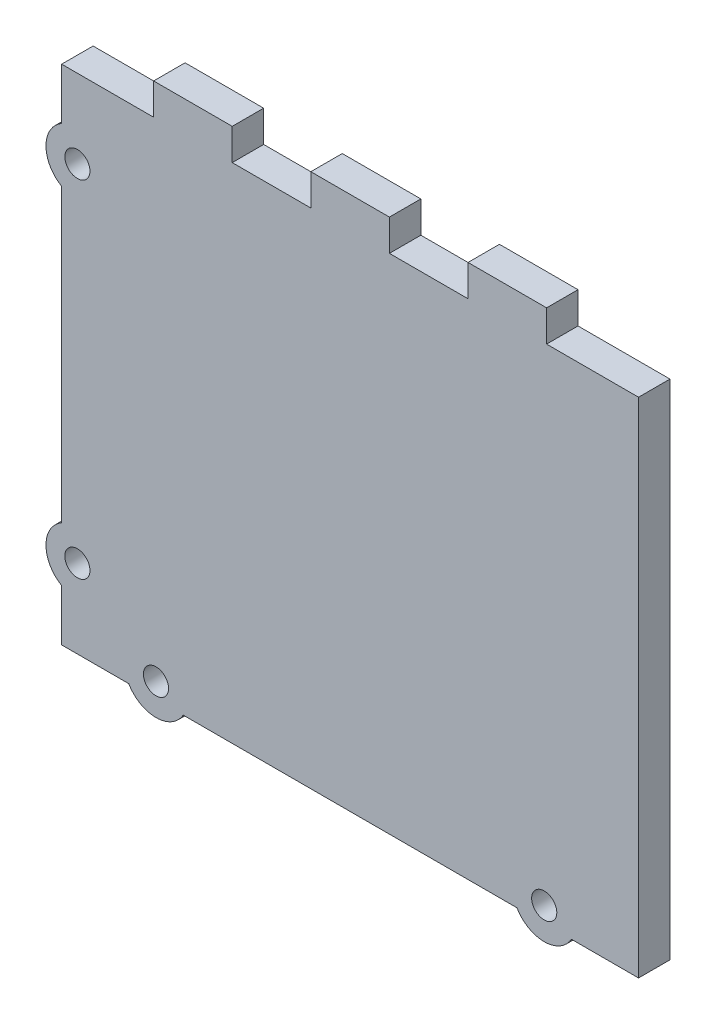
SolidWorks part; units mm, degrees
ref_plane "Front Plane" through (0, 0, 0) normal (0, 0, 1) x (1, 0, 0)
ref_plane "Top Plane" through (0, 0, 0) normal (0, 1, 0) x (1, 0, 0)
ref_plane "Right Plane" through (0, 0, 0) normal (1, 0, 0) x (0, 0, -1)
sketch "Sketch1" plane through (0, 0, 0) normal (0, 0, 1) x (1, 0, 0)
  line L0 (-23, -34.2) -> (-36.4, -34.2) construction
  line L2 (-36.5, 29.8) -> (-36.5, -34.2)
  line L3 (-36.5, -34.2) -> (36.9, -34.2)
  line L4 (36.9, 29.8) -> (36.9, -34.2)
  line L5 (-36.5, 29.8) -> (36.9, 29.8)
  line L7 (-36.5, -17) -> (-36.5, 16.6) construction
  point P0 (0, 0)
extrude "Boss-Extrude1" add sketch "Sketch1" along normal blind 4
sketch "Sketch2" plane through (0, 0, 4) normal (0, 0, 1) x (1, 0, 0)
  line L0 (-36.5, -34.2) -> (36.9, -34.2) construction
  line L1 (26.5, -34.2) -> (23.3, -34.2) construction
  line L2 (-36.5, 29.8) -> (-36.5, -34.2) construction
  line L4 (-32.5, 16.6) -> (-36.5, 16.6) construction
  line L5 (-36.5, 16.3359) -> (-36.5, 23.2641)
  line L6 (28.3665, -34.2) -> (21.4335, -34.2)
  circle A0 centre (24.9, -32.2042) radius 1.6
  arc A1 (28.3665, -34.2) -> (21.4335, -34.2) centre (24.9, -32.2042) cw
  circle A2 centre (-34.5, 19.8) radius 1.6
  arc A3 (-36.5, 16.3359) -> (-36.5, 23.2641) centre (-34.5, 19.8) cw
  point P9 (24.9, -34.2)
  line M6 (-36.5, 29.8) -> (-36.5, -34.2)
  line M7 (-36.5, -34.2) -> (36.9, -34.2)
  dimension "D1" = 3.2
  dimension "D2" = 4
  dimension "D4" = 3.2
  dimension "D6" = 4
  dimension "D7" = 3.2
  dimension "D3" = 1.9958
  dimension "D5" = 2
extrude "Boss-Extrude2" add sketch "Sketch2" against normal blind 4 contours A1 M7 region at (24.9, -35.0219, 4)
extrude "Cut-Extrude1" cut sketch "Sketch2<3>" against normal blind 4 contours A0 region at (24.9, -32.2042, 4)
sketch "Sketch2<3>" plane through (0, 0, 4) normal (0, 0, 1) x (1, 0, 0) same geometry as "Sketch2"
ref_plane "Plane1" through (0.2, 0, 0) normal (1, 0, 0) x (0, 0, -1)
mirror "Mirror1" about plane through (0.2, 0, 0) normal (1, 0, 0) of "Cut-Extrude1", "Boss-Extrude2"
ref_plane "Plane2" through (0, -2.2, 0) normal (0, -1, 0) x (-1, 0, 0)
extrude "Boss-Extrude3" add sketch "Sketch2<4>" against normal blind 4 contours A3 M6 region at (-37.3201, 19.8, 4)
sketch "Sketch2<4>" plane through (0, 0, 4) normal (0, 0, 1) x (1, 0, 0) same geometry as "Sketch2"
extrude "Cut-Extrude2" cut sketch "Sketch2<5>" against normal blind 4 contours A2 region at (-34.5, 19.8, 4)
sketch "Sketch2<5>" plane through (0, 0, 4) normal (0, 0, 1) x (1, 0, 0) same geometry as "Sketch2"
mirror "Mirror3" about plane through (0, -2.2, 0) normal (0, -1, 0) of "Boss-Extrude3", "Cut-Extrude2"
sketch "Sketch3" plane through (0, 0, 0) normal (0, 0, -1) x (-1, 0, 0)
  line L1 (-25.2, 29.3) -> (-15.2, 29.3)
  line L2 (-25.2, 29.3) -> (-25.2, 33.8)
  line L3 (-25.2, 33.8) -> (-15.2, 33.8)
  line L4 (-15.2, 29.3) -> (-15.2, 33.8)
  line L5 (-36.9, -34.2) -> (-36.9, 29.8) construction
  line L6 (4.8, 29.3) -> (4.8, 33.8)
  line L7 (-5.2, 33.8) -> (4.8, 33.8)
  line L8 (-5.2, 29.3) -> (-5.2, 33.8)
  line L9 (-5.2, 29.3) -> (4.8, 29.3)
  line L10 (24.8, 29.3) -> (24.8, 33.8)
  line L11 (14.8, 33.8) -> (24.8, 33.8)
  line L12 (14.8, 29.3) -> (14.8, 33.8)
  line L13 (14.8, 29.3) -> (24.8, 29.3)
  line L15 (-36.9, 29.8) -> (36.5, 29.8) construction
  dimension "D1" = 11.7
  dimension "D2" = 10
  dimension "D3" = 4.5
  dimension "D5" = 4
  dimension "D4" = 3
extrude "Boss-Extrude4" add sketch "Sketch3" against normal blind 4 separate body
combine bodies "Combine1" operation type add bodies to combine 109 108 110 111
